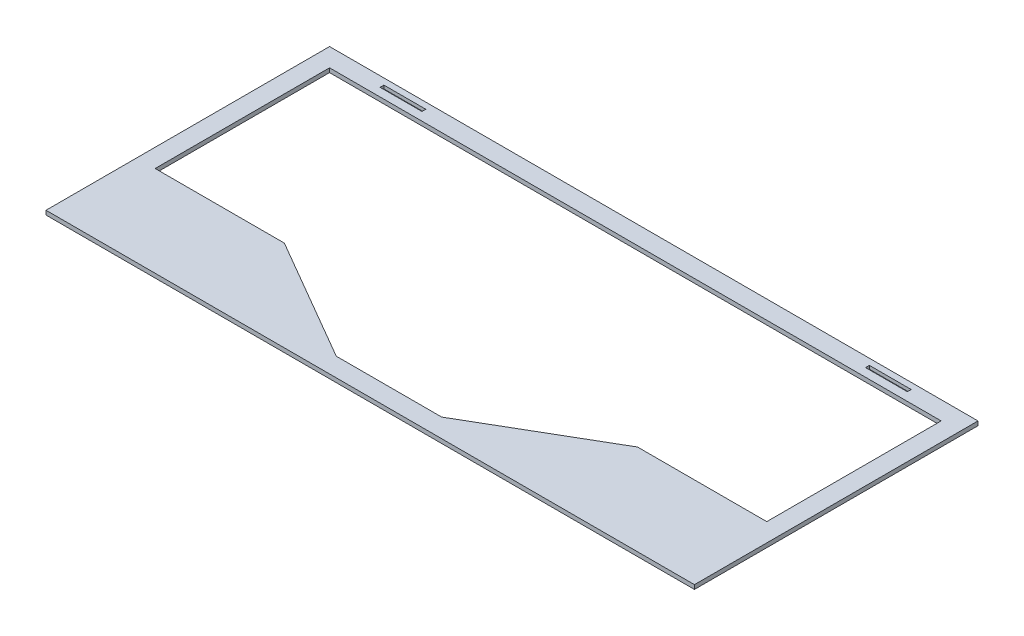
SolidWorks part; units mm, degrees
ref_plane "Front Plane" through (0, 0, 0) normal (0, 0, 1) x (1, 0, 0)
ref_plane "Top Plane" through (0, 0, 0) normal (0, 1, 0) x (1, 0, 0)
ref_plane "Right Plane" through (0, 0, 0) normal (1, 0, 0) x (0, 0, -1)
sketch "Sketch1" plane through (0, 0, 0) normal (0, 1, 0) x (1, 0, 0)
  line L1 (-193.7, 84.7) -> (193.7, 84.7)
  line L2 (-193.7, 84.7) -> (-193.7, -84.7)
  line L3 (-193.7, -84.7) -> (193.7, -84.7)
  line L4 (193.7, 84.7) -> (193.7, -84.7)
  line L5 (-193.7, 84.7) -> (193.7, -84.7) construction
  line L6 (-193.7, -84.7) -> (193.7, 84.7) construction
  point P0 (0, 0)
  dimension "D1" = 387.4
  dimension "D2" = 169.4
extrude "Boss-Extrude1" add sketch "Sketch1" along normal blind 2.5
sketch "Sketch2" plane through (0, 2.5, 0) normal (0, 1, 0) x (1, 0, 0)
  line L0 (0, 78.7) -> (0, 84.7) construction
  line L2 (-187.7, 78.7) -> (187.7, 78.7)
  line L3 (-187.7, 78.7) -> (-187.7, -78.7)
  line L4 (-187.7, -78.7) -> (187.7, -78.7)
  line L5 (187.7, 78.7) -> (187.7, -78.7)
  line L6 (-187.7, 78.7) -> (187.7, -78.7) construction
  line L7 (-187.7, -78.7) -> (187.7, 78.7) construction
  line L8 (193.7, 84.7) -> (-193.7, 84.7) construction
  line L9 (187.7, 0) -> (193.7, 0) construction
  line L10 (193.7, -84.7) -> (193.7, 84.7) construction
  point P0 (0, 0)
  dimension "D1" = 6
  dimension "D2" = 6
extrude "Cut-Extrude1" [suppressed] cut sketch "Sketch2" against normal offset from surface (1 mm away) 1.5 up to face at (0, 0, 0)
sketch "Sketch3" plane through (0, 2.5, 0) normal (0, 1, 0) x (1, 0, 0)
  line L0 (193.7, 84.7) -> (157.5, 84.7) construction
  line L1 (193.7, 84.7) -> (-193.7, 84.7) construction
  line L2 (157.5, 81) -> (157.5, 78.7)
  line L4 (157.5, 78.7) -> (132.5, 78.7)
  line L6 (132.5, 78.7) -> (132.5, 81)
  line L7 (132.5, 81) -> (157.5, 81)
  line L8 (157.5, 84.7) -> (157.5, 78.7) construction
  line L9 (-193.7, 84.7) -> (-157.5, 84.7) construction
  line L10 (-157.5, 81) -> (-157.5, 78.7)
  line L11 (-157.5, 78.7) -> (-132.5, 78.7)
  line L12 (-132.5, 78.7) -> (-132.5, 81)
  line L13 (-132.5, 81) -> (-157.5, 81)
  line L14 (-157.5, 84.7) -> (-157.5, 78.7) construction
  point P7 (0, 0)
  dimension "D1" = 36.2
  dimension "D2" = 2.3
  dimension "D3" = 25
  dimension "D4" = 36.2
  dimension "D5" = 2.3
  dimension "D6" = 25
  dimension "D7" = 6
  dimension "D8" = 6
extrude "Cut-Extrude2" cut sketch "Sketch3" against normal blind 2
sketch "Sketch4" plane through (0, 0, 0) normal (0, -1, 0) x (1, 0, 0)
  line L0 (31.5, 73.5) -> (105.5, 30.5)
  line L1 (105.5, 30.5) -> (182.7, 30.5)
  line L2 (182.7, 30.5) -> (182.7, -73.7)
  line L3 (182.7, -73.7) -> (-182.7, -73.7)
  line L4 (-182.7, -73.7) -> (-182.7, 30.5)
  line L5 (-182.7, 30.5) -> (-105.5, 30.5)
  line L6 (-105.5, 30.5) -> (-31.5, 73.5)
  line L7 (-31.5, 73.5) -> (31.5, 73.5)
  line L8 (-144.1, 30.5) -> (-144.1, 84.7) construction
  line L9 (-193.7, 84.7) -> (193.7, 84.7) construction
  line L10 (0, 73.5) -> (0, 84.7) construction
  line L11 (144.1, 30.5) -> (144.1, 84.7) construction
  line L12 (0, -73.7) -> (0, -84.7) construction
  line L13 (193.7, -84.7) -> (-193.7, -84.7) construction
  line L14 (-182.7, -21.6) -> (-193.7, -21.6) construction
  line L15 (-193.7, -84.7) -> (-193.7, 84.7) construction
  line L16 (182.7, -21.6) -> (193.7, -21.6) construction
  line L17 (193.7, 84.7) -> (193.7, -84.7) construction
  line L18 (-105.5, 30.5) -> (-105.5, 35.5) construction
  line L19 (105.5, 30.5) -> (105.5, 35.5) construction
  dimension "D1" = 54.2
  dimension "D2" = 11.2
  dimension "D3" = 11
  dimension "D4" = 11
extrude "Cut-Extrude3" cut sketch "Sketch4" against normal blind 10
equation "\"full_width\"=375"
equation "\"D1@Sketch1\"=\"full_width\"+(\"added_width\"*2)+(\"margin1\"*2)"
equation "\"added_width\"=6"
equation "\"full_height\"= 157"
equation "\"D2@Sketch1\"=\"full_height\"+(\"added_height\"*2)+(\"margin1\"*2)"
equation "\"added_height\"=6"
equation "\"D1@Sketch3\"=30.00mm+\"added_width\"+\"margin1\""
equation "\"tab_depth\"=2.5"
equation "\"D2@Sketch3\"=\"tab_depth\"-\"margin1\""
equation "\"tab_width\"=25"
equation "\"D3@Sketch3\"=\"tab_width\""
equation "\"tab_height\"=2"
equation "\"D1@Cut-Extrude2\"=\"tab_height\""
equation "\"D4@Sketch3\"=30mm+\"added_width\"+\"margin1\""
equation "\"D5@Sketch3\"=\"tab_depth\"-\"margin1\""
equation "\"D6@Sketch3\"=\"tab_width\""
equation "\"D2@Sketch2\"=\"added_height\""
equation "\"D1@Sketch2\"=\"added_width\""
equation "\"margin1\"= 0.2"
equation "\"angle_dist\"=32.037"
equation "\"chin_dist\"=6.2"
equation "\"D2@Sketch4\"=\"chin_dist\"+5"
equation "\"flat_dist\"=49.2"
equation "\"D1@Sketch4\"=\"flat_dist\"+5"
equation "\"D3@Sketch4\"=\"added_height\"+5"
equation "\"D4@Sketch4\"=\"added_width\"+5"
equation "\"D7@Sketch3\"=\"added_height\""
equation "\"D8@Sketch3\"=\"added_height\""
